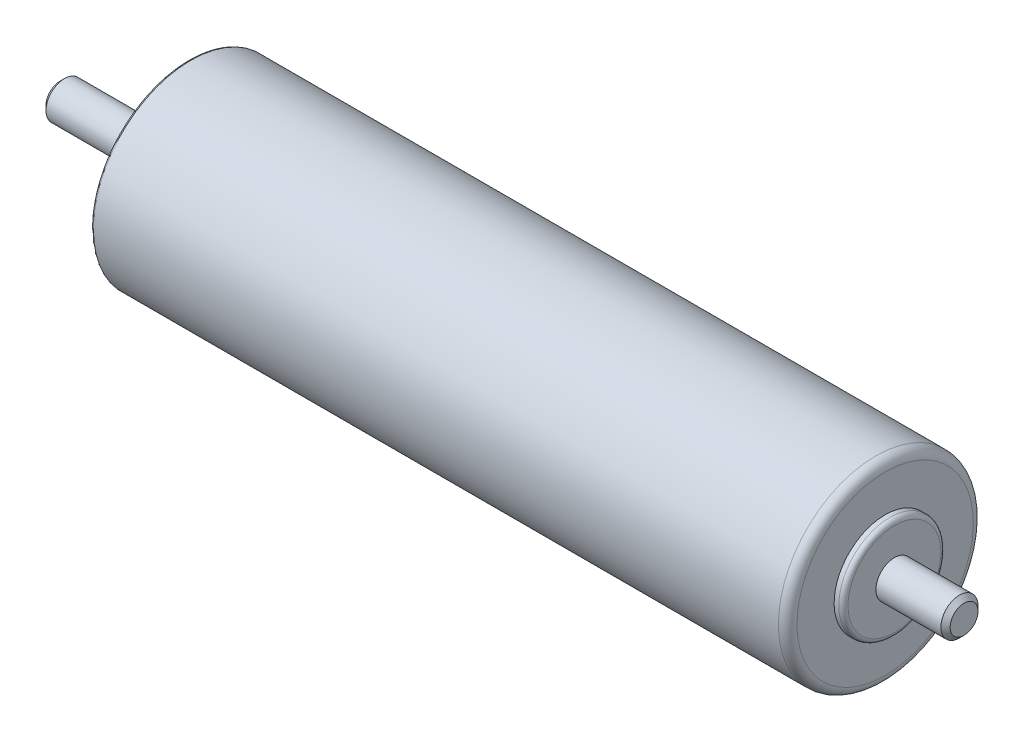
SolidWorks part; units mm, degrees
material "3.0505 (EN-AW 3105)"
ref_plane "Plan de face" through (0, 0, 0) normal (0, 0, 1) x (1, 0, 0)
ref_plane "Plan de dessus" through (0, 0, 0) normal (0, 1, 0) x (1, 0, 0)
ref_plane "Plan de droite" through (0, 0, 0) normal (1, 0, 0) x (0, 0, -1)
sketch "Esquisse1" plane through (0, 0, 0) normal (0, 0, 1) x (1, 0, 0)
  line L0 (0, 0) -> (0, 4)
  line L1 (0, 4) -> (25, 4)
  line L2 (25, 4) -> (25, 12.5)
  line L3 (25, 12.5) -> (27.8, 12.5)
  line L4 (27.8, 12.5) -> (27.8, 21)
  line L5 (27.8, 21) -> (177.8, 21)
  line L6 (177.8, 21) -> (177.8, 11)
  line L7 (177.8, 11) -> (179.8, 11)
  line L8 (179.8, 11) -> (179.8, 4)
  line L9 (179.8, 4) -> (194.8, 4)
  line L10 (194.8, 4) -> (194.8, 0)
  line L11 (194.8, 0) -> (0, 0)
  dimension "D1" = 150
  dimension "D2" = 4
  dimension "D3" = 12.5
  dimension "D4" = 15
  dimension "D5" = 21
  dimension "D6" = 2.8
  dimension "D7" = 2
  dimension "D8" = 25
  dimension "D9" = 4
  dimension "D10" = 11
revolve "Révolution1" add sketch "Esquisse1" angle 360 about L11
fillet "Congé3" radius 2 1 edges at (177.8, 21, 0)
fillet "Congé4" radius 1 1 edges at (25, 12.5, 0)
fillet "Congé5" radius 1 1 edges at (179.8, 11, 0)
chamfer "Chanfrein2" distance 1 angle 45 1 edges at (0, 4, 0)
chamfer "Chanfrein3" distance 1 angle 45 1 edges at (194.8, 4, 0)
ref_axis "Axe1" through (29.8, 0, 0) along (1, 0, 0)
hole_wizard "Trou taraudé M3x0.51" positions "Esquisse7" profile "Esquisse6" tap size "M3x0.5" standard "Ansi Métrique"
sketch "Esquisse7" plane through (27.8, 0, 0) normal (-1, 0, 0) x (0, 0, 1)
  point P0 (16, -0.2482)
  dimension "D1" = 16
sketch "Esquisse6" plane through (27.8, -0.2482, 16) normal (0, 1, 0) x (0, 0, 1)
  line L0 (0, 0) -> (0, 9.2511)
  line L1 (0, 9.2511) -> (1.25, 8.5)
  line L2 (1.25, 8.5) -> (1.25, 0)
  line L5 (1.25, 0) -> (0, 0)
  line L10 (0, 9.2511) -> (-1.25, 8.5) construction
  line L11 (0, -6.35) -> (0, 107.95) construction
  dimension "Diamètre du trou pour taraudage" = 2.5
  dimension "Profondeur du trou pour taraudage" = 8.5
  dimension "Angle de pointe" = 118
cosmetic thread "Filetage de perçage1" parameters "D1"=6, "D2"=3
pattern_circular "Répétition circulaire1" count 4 over 360 about axis through (29.8, 0, 0) along (1, 0, 0) of "Trou taraudé M3x0.51"
fillet "Congé6" radius 0.4 1 edges at (27.8, 21, 0)
ref_axis "Axe4" through (36.3, 16, 0.2482) along (-1, 0, 0)
ref_axis "Axe5" through (36.3, -16, -0.2482) along (-1, 0, 0)
ref_axis "Axe6" through (36.3, -0.2482, 16) along (-1, 0, 0)
sketch "Esquisse21" plane through (27.8, 0, 0) normal (-1, 0, 0) x (0, 0, 1)
  line L0 (14.0679, -0.2182) -> (17.9978, -0.2792) construction
  line L1 (16, -0.2482) -> (0, 0) construction
  line L2 (-0.2482, -16) -> (0, 0) construction
  line L3 (-0.2482, -16) -> (-0.2792, -17.9978) construction
  circle A0 centre (0, 0) radius 18
  dimension "D1" = 36
sketch "Esquisse23" plane through (27.8, 0, 0) normal (-1, 0, 0) x (0, 0, 1)
  circle A2 centre (0, 0) radius 18 construction
  point P0 (12.529, -12.9238)
  dimension "D1" = 45
hole_wizard "Trou taraudé M4x0.72" positions "Esquisse25" profile "Esquisse24" tap size "M4x0.7" standard "Ansi Métrique"
sketch "Esquisse25" plane through (27.8, 0, 0) normal (-1, 0, 0) x (0, 0, 1)
  point P0 (12.529, -12.9238)
  dimension "D1" = 18
sketch "Esquisse24" plane through (27.8, -12.9238, 12.529) normal (0, 1, 0) x (0, 0, 1)
  line L0 (0, 0) -> (0, 13.4914)
  line L1 (0, 13.4914) -> (1.65, 12.5)
  line L2 (1.65, 12.5) -> (1.65, 0)
  line L5 (1.65, 0) -> (0, 0)
  line L10 (0, 13.4914) -> (-1.65, 12.5) construction
  line L11 (0, -6.35) -> (0, 107.95) construction
  dimension "Diamètre du trou pour taraudage" = 3.3
  dimension "Profondeur du trou pour taraudage" = 12.5
  dimension "Angle de pointe" = 118
cosmetic thread "Filetage de perçage3" parameters "D1"=9, "D2"=4
pattern_circular "Répétition circulaire2" count 4 over 360 about axis through (29.8, 0, 0) along (1, 0, 0) of "Trou taraudé M4x0.72"
